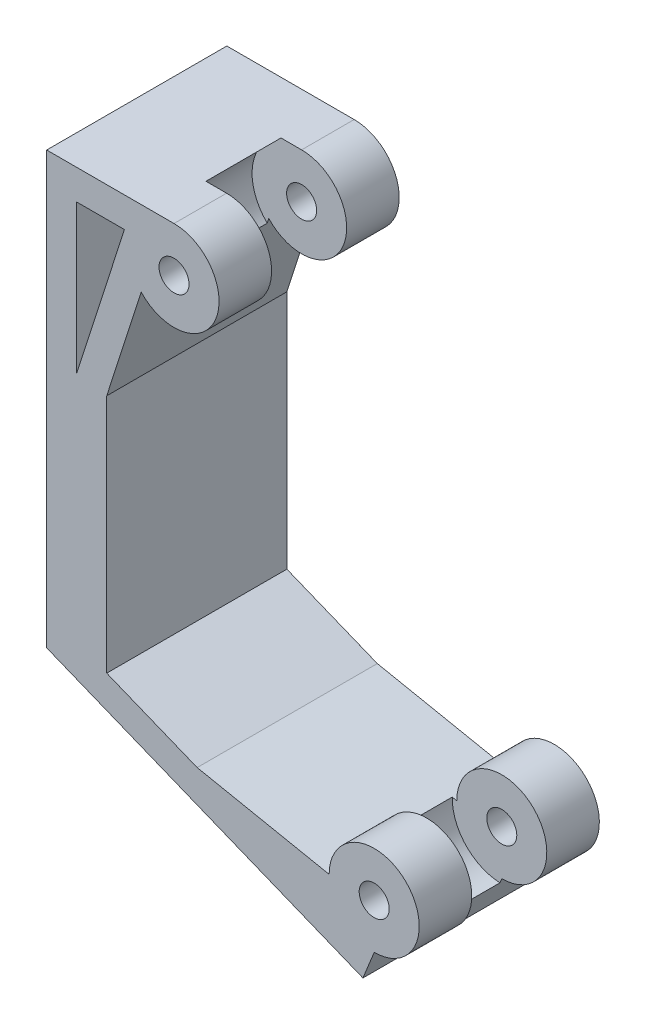
SolidWorks part; units mm, degrees
other "Markup1"
sketch "Sketch3" plane through (0, 0, 12) normal (0, 0, 1) x (1, 0, 0)
other "DetailItem1"
other "DetailItem3"
other "DetailItem5"
ref_plane "Front Plane" through (0, 0, 0) normal (0, 0, 1) x (1, 0, 0)
ref_plane "Top Plane" through (0, 0, 0) normal (0, 1, 0) x (1, 0, 0)
ref_plane "Right Plane" through (0, 0, 0) normal (1, 0, 0) x (0, 0, -1)
sketch "Sketch1" plane through (0, 0, 0) normal (0, 0, 1) x (1, 0, 0)
  line L2 (0, 6.6577) -> (0, 35.3819)
  line L3 (0, 35.3819) -> (8.4836, 35.3819)
  line L5 (6.2976, 30.3272) -> (4, 23.2001)
  line L6 (4, 23.2001) -> (4, 7.1987)
  line L7 (10.0251, 4.7644) -> (18.8174, 3)
  line L11 (8.4836, 32.3819) -> (21.8174, 3) construction
  line L12 (5.181, 33.3819) -> (2, 33.3819)
  line L13 (2, 33.3819) -> (2, 23.5145)
  line L14 (2, 23.5145) -> (5.181, 33.3819)
  line L15 (8.4836, 32.3819) -> (8.4836, 5.1119) construction
  line L16 (8.4836, 5.1119) -> (21.8174, 3) construction
  line L17 (8.4836, 5.1119) -> (8.4836, -11.812) construction
  line L21 (4, 7.1987) -> (10.0251, 4.7644)
  line L22 (-988.8605, 0) -> (16.4784, 0) construction
  line L23 (0, 6.6577) -> (21.0681, -1.8544)
  line L24 (-906.1157, 372.7522) -> (46380.2609, -18732.184) construction
  line L25 (21.8174, 0) -> (50021.8174, 0) construction
  line L26 (21.8174, 0) -> (21.0681, -1.8544)
  line L27 (-905.3665, 374.6066) -> (46381.0101, -18730.3297) construction
  arc A0 (21.8174, 0) -> (18.8174, 3) centre (21.8174, 3) ccw
  arc A1 (8.4836, 35.3819) -> (6.2976, 30.3272) centre (8.4836, 32.3819) cw
  circle A2 centre (8.4836, 32.3819) radius 1
  circle A3 centre (21.8174, 3) radius 1
  dimension "D1" = 2
  dimension "D3" = 3
  dimension "D2" = 4
  dimension "D6" = 2
  dimension "D4" = 27.27
  dimension "D5" = 13.5
  dimension "D8" = 81
  dimension "D11" = 2
  dimension "D7" = 2
  dimension "D12" = 22
  dimension "D13" = 2
extrude "Boss-Extrude1" add sketch "Sketch1" along normal blind 12
ref_plane "midplane" through (0, 0, 6) normal (0, 0, 1) x (1, 0, 0)
sketch "Sketch2" plane through (0, 0, 6) normal (0, 0, 1) x (1, 0, 0)
  circle A0 centre (8.4836, 32.3819) radius 3.3
  circle A1 centre (21.8174, 3) radius 3.3
  dimension "D1" = 6.6
extrude "Cut-Extrude1" cut sketch "Sketch2" against normal blind 2.5 and the other way blind 2.5
equation "\"axle-diameter\"=2"
equation "\"D1@Sketch1\"=\"axle-diameter\""
equation "\"switch-thickness\"=12"
equation "\"D1@Boss-Extrude1\"=\"switch-thickness\""
equation "\"base-width\"=4.0"
equation "\"D2@Sketch1\"=\"base-width\""
equation "\"axle-bushing-radius\"=3"
equation "\"D3@Sketch1\"= \"axle-bushing-radius\""
equation "\"D1@Sketch2\"=\"axle-bushing-radius\"*2.2"
equation "\"D1@Cut-Extrude1\"=\"switch-thickness\"/6+\"clearance\""
equation "\"D2@Cut-Extrude1\"=\"switch-thickness\"/6+\"clearance\""
equation "\"clearance\"= 0.5"
equation "\"arm-width\"=3.0"
